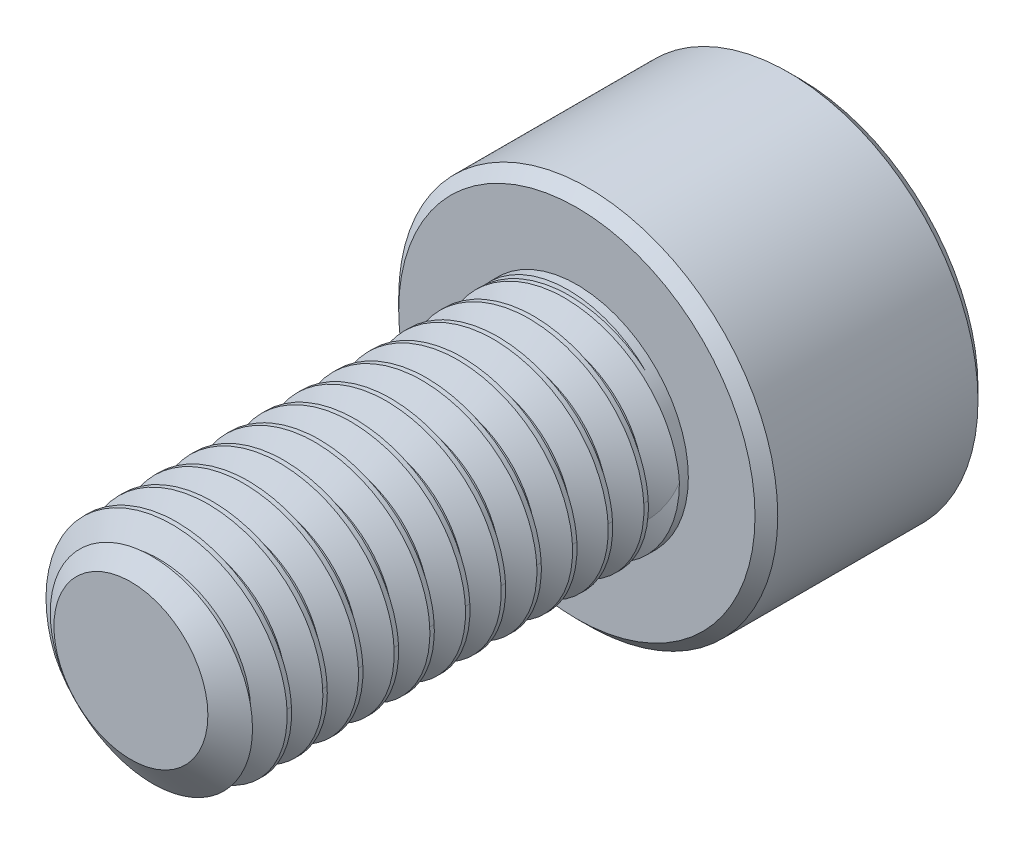
SolidWorks part; units mm, degrees
material "Alloy Steel"
ref_plane "Front Plane" through (0, 0, 0) normal (0, 0, 1) x (1, 0, 0)
ref_plane "Top Plane" through (0, 0, 0) normal (0, 1, 0) x (1, 0, 0)
ref_plane "Right Plane" through (0, 0, 0) normal (1, 0, 0) x (0, 0, -1)
sketch "Sketch1" plane through (0, 0, 0) normal (0, 0, 1) x (1, 0, 0)
  circle A0 centre (0, 0) radius 2.5
  dimension "OD" = 5
extrude "Extrude1" add sketch "Sketch1" against normal blind 10
sketch "Sketch2" plane through (0, 0, 0) normal (0, 0, 1) x (1, 0, 0)
  circle A0 centre (0, 0) radius 2.5 construction
  circle A1 centre (0, 0) radius 2.5
curve "Helix/Spiral1" pitch 0.8 height 10.8 turns 13.5 parameters "pitch"=0.8
sketch "Sketch3" plane through (0, 0, 0) normal (1, 0, 0) x (0, 0, -1)
  line L0 (-0.7, 2.5) -> (-0.4, 1.9804)
  line L1 (-0.4, 1.9804) -> (-0.3, 1.9804)
  line L2 (-0.3, 1.9804) -> (0, 2.5)
  line L3 (-0.7, 2.5) -> (0, 2.5)
  line L4 (-0.35, 2.5) -> (-0.35, 1.9804) construction
  line L5 (-0.55, 2.2402) -> (-0.15, 2.2402) construction
  line L6 (0, 2.5) -> (0, -2.5) construction
  line L7 (0, -2.5) -> (10, -2.5) construction
  point P11 (3.6, -2.5)
  dimension "D1" = 0.1
  dimension "D2" = 0.4
  dimension "D3" = 60
  dimension "D4" = 3.6
sweep "Cut-Sweep1" cut profiles "Sketch3" path "Helix/Spiral1"
sketch "Sketch4" plane through (0, 0, 0) normal (1, 0, 0) x (0, 0, -1)
  line L0 (0.5417, 2.5) -> (0, 1.7264)
  line L1 (0, 1.7264) -> (0, 2.5)
  line L2 (0.5417, 2.5) -> (0, 2.5)
  line L3 (-0.7, 2.5) -> (0, 2.5) construction
  line L4 (0, 0) -> (7.0209, 0) construction
  dimension "D1" = 55
  dimension "D2" = 0.254
revolve "Cut-Revolve1" cut sketch "Sketch4" angle 360 about L4
sketch "Sketch5" plane through (0, 0, 0) normal (1, 0, 0) x (0, 0, -1)
  line L0 (10, -1.7838) -> (10, 1.991) construction
  line L1 (10, 2.5) -> (0.1203, 2.5)
  line L2 (10, 2.5) -> (10, 0)
  line L3 (10, 0) -> (0.0001, 0)
  line L4 (0.0001, 2.1698) -> (0.0001, 0)
  line L5 (0.1203, 2.5) -> (0.0001, 2.1698)
  line L6 (0, 0) -> (9.9695, 0) construction
  point P3 (0.0001, 2.5)
  point P10 (0.0001, 2.5)
  dimension "D1" = 0.3302
  dimension "Thread min" = 0.0001
  dimension "D3" = 20
revolve "partially thread" [suppressed] add sketch "Sketch5" angle 360 about L6
sketch "Sketch6" plane through (0, 0, -10) normal (0, 0, -1) x (-1, 0, 0)
  circle A0 centre (0, 0) radius 4.25
  dimension "head dia" = 8.5
extrude "Extrude2" add sketch "Sketch6" along normal blind 5
sketch "Sketch7" plane through (0, 0, -15) normal (0, 0, -1) x (-1, 0, 0)
  line L1 (0, 2.3094) -> (-2, 1.1547)
  line L2 (-2, 1.1547) -> (-2, -1.1547)
  line L3 (-2, -1.1547) -> (0, -2.3094)
  line L4 (0, -2.3094) -> (2, -1.1547)
  line L5 (2, -1.1547) -> (2, 1.1547)
  line L6 (2, 1.1547) -> (0, 2.3094)
  circle A0 centre (0, 0) radius 2 construction
  dimension "hex dia" = 4
extrude "Cut-Extrude1" cut sketch "Sketch7" against normal blind 3
sketch "Sketch8" plane through (0, 0, -15) normal (0, 0, -1) x (-1, 0, 0)
  circle A0 centre (0, 0) radius 2.3094
extrude "Cut-Extrude2" cut sketch "Sketch8" against normal through all draft 45
chamfer "Chamfer1" distance 0.255 angle 45 2 edges at (-4.25, 0, -15) (-4.25, 0, -10)
sketch "Sketch9" plane through (0, 0, 0) normal (1, 0, 0) x (0, 0, -1)
  line L0 (0, 2.5) -> (0, -2.5) construction
  line L1 (4.4, 2.5) -> (4.4, -2.5) construction
  dimension "D1" = 4.4
sketch "Sketch10" plane through (0, 0, 0) normal (1, 0, 0) x (0, 0, -1)
  line L0 (10, 2.5) -> (10, 0)
  line L1 (10, 2.5) -> (9.8, 2.5)
  line L2 (9.8, 2.5) -> (8.7645, 0)
  line L3 (10, 0) -> (8.7645, 0)
  line L4 (10, 3.995) -> (10, -3.995) construction
  dimension "D1" = 22.5
  dimension "D2" = 0.2
revolve "Revolve1" add sketch "Sketch10" angle 360 about L3
equation "\"D3@Helix/Spiral1\" = \"screw length@Extrude1\"+\"pitch@Helix/Spiral1\""
equation "\"D1@Sketch3\" = \"pitch@Helix/Spiral1\"*.125"
equation "\"D2@Sketch3\" = \"pitch@Helix/Spiral1\"*.5"
equation "\"D1@Cut-Extrude1\" = \"hex dia@Sketch7\"*.75"
equation "\"D1@Chamfer1\" = \"head dia@Sketch6\"*.03"
equation "\"D1@Sketch9\" = \"pitch@Helix/Spiral1\"*5.5"
equation "\"D2@Sketch10\" = \"pitch@Helix/Spiral1\"*.25"
equation "\"D4@Sketch3\" = \"pitch@Helix/Spiral1\"*4.50"
